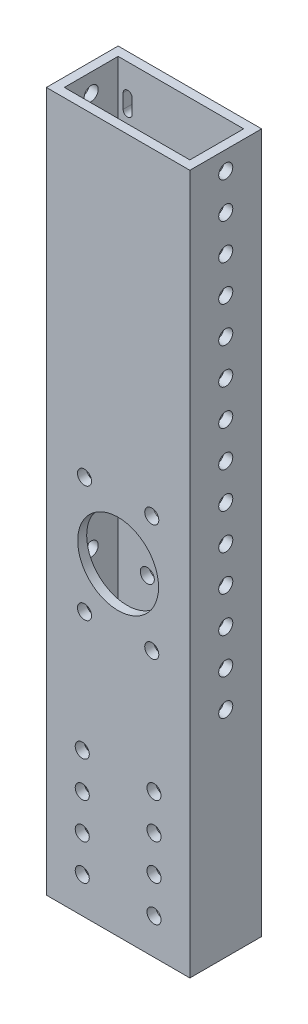
SolidWorks part; units mm, degrees
material "6061-T6 (SS)"
ref_plane "Alzado" through (0, 0, 0) normal (0, 0, 1) x (1, 0, 0)
ref_plane "Planta" through (0, 0, 0) normal (0, 1, 0) x (1, 0, 0)
ref_plane "Vista lateral" through (0, 0, 0) normal (1, 0, 0) x (0, 0, -1)
sketch "Croquis1" plane through (0, 0, 0) normal (0, 1, 0) x (1, 0, 0)
  line L1 (-101.6, -12.7) -> (101.6, -12.7)
  line L2 (-101.6, -12.7) -> (-101.6, 12.7)
  line L3 (-101.6, 12.7) -> (101.6, 12.7)
  line L4 (101.6, -12.7) -> (101.6, 12.7)
  line L5 (-101.6, -12.7) -> (101.6, 12.7) construction
  line L6 (-101.6, 12.7) -> (101.6, -12.7) construction
  point P0 (0, 0)
  dimension "D1" = 25.4
  dimension "D2" = 203.2
extrude "Saliente-Extruir1" add sketch "Croquis1" along normal blind 25.4
shell "Vaciado1" thickness 3.175 removed face at (-101.6, 12.7, 0) removed face at (101.6, 12.7, 0)
sketch "Croquis2" plane through (0, 25.4, 0) normal (0, 1, 0) x (1, 0, 0)
  line L0 (101.6, 12.7) -> (-101.6, 12.7) construction
  line L1 (-25.4, -12.7) -> (25.4, -12.7)
  line L2 (-25.4, -12.7) -> (-25.4, 12.7)
  line L3 (-25.4, 12.7) -> (25.4, 12.7)
  line L4 (25.4, -12.7) -> (25.4, 12.7)
  line L5 (-25.4, -12.7) -> (25.4, 12.7) construction
  line L6 (-25.4, 12.7) -> (25.4, -12.7) construction
  line L8 (-22.225, -9.525) -> (22.225, -9.525)
  line L9 (-22.225, -9.525) -> (-22.225, 9.525)
  line L10 (-22.225, 9.525) -> (22.225, 9.525)
  line L11 (22.225, -9.525) -> (22.225, 9.525)
  line L12 (-22.225, -9.525) -> (22.225, 9.525) construction
  line L13 (-22.225, 9.525) -> (22.225, -9.525) construction
  point P0 (0, 0)
  point P8 (0, 0)
  dimension "D1" = 50.8
  dimension "D2" = 3.175
  dimension "D3" = 3.175
extrude "Saliente-Extruir2" add sketch "Croquis2" along normal blind 247.65 separate body
sketch "Croquis3" plane through (0, 25.4, 0) normal (0, 1, 0) x (1, 0, 0)
  line L0 (0, 0) -> (0, 12.7) construction
  line L1 (25.4, 12.7) -> (-25.4, 12.7) construction
  circle A0 centre (-47.625, 0) radius 3.2639
  circle A1 centre (-79.375, 0) radius 3.2639
  circle A2 centre (79.375, 0) radius 3.2639
  circle A3 centre (47.625, 0) radius 3.2639
  dimension "D1" = 47.625
  dimension "D2" = 6.5278
  dimension "D3" = 31.75
extrude "Cortar-Extruir1" cut sketch "Croquis3" against normal through all
sketch "Croquis4" plane through (0, 0, 12.7) normal (0, 0, 1) x (1, 0, 0)
  line L0 (0, 25.4) -> (0, 139.6619) construction
  line L1 (-101.6, 25.4) -> (101.6, 25.4) construction
  line L2 (0, 139.6619) -> (-23.8125, 139.6619) construction
  circle A0 centre (0, 139.6619) radius 14.3129
  circle A1 centre (0, 139.6619) radius 23.8125 construction
  circle A2 centre (-23.8125, 139.6619) radius 2.4892 construction
  circle A3 centre (-11.9062, 160.2841) radius 2.4892
  circle A4 centre (11.9063, 160.2841) radius 2.4892
  circle A5 centre (23.8125, 139.6619) radius 2.4892 construction
  circle A6 centre (11.9062, 119.0397) radius 2.4892
  circle A7 centre (-11.9063, 119.0397) radius 2.4892
  dimension "D1" = 28.6258
  dimension "D3" = 47.625
  dimension "D4" = 4.9784
  dimension "D2" = 114.2619
  dimension "D6" = 23.8125
  dimension "D5" = 6
extrude "Cortar-Extruir2" cut sketch "Croquis4" against normal through all
sketch "Croquis8" plane through (0, 0, 12.7) normal (0, 0, 1) x (1, 0, 0)
  line L0 (0, 0) -> (0, 273.05) construction
  line L1 (-101.6, 12.7) -> (0, 12.7) construction
  line L2 (-101.6, 25.4) -> (-101.6, 0) construction
  line L3 (0, 12.7) -> (-12.7, 12.7) construction
  line L4 (0, 12.7) -> (12.7, 12.7) construction
  line L5 (-25.4, 273.05) -> (25.4, 273.05) construction
  line L6 (-12.7, 12.7) -> (-12.7, 25.4) construction
  circle A0 centre (0, 12.7) radius 2.4892
  circle A1 centre (-12.7, 12.7) radius 2.4892
  circle A2 centre (-25.4, 12.7) radius 2.4892
  circle A3 centre (-38.1, 12.7) radius 2.4892
  circle A4 centre (-50.8, 12.7) radius 2.4892
  circle A5 centre (0, 12.7) radius 2.4892
  circle A6 centre (-12.7, 12.7) radius 2.4892
  circle A7 centre (-25.4, 12.7) radius 2.4892
  circle A8 centre (-38.1, 12.7) radius 2.4892
  circle A9 centre (12.7, 12.7) radius 2.4892
  circle A10 centre (0, 12.7) radius 2.4892
  circle A11 centre (-12.7, 12.7) radius 2.4892
  circle A12 centre (-25.4, 12.7) radius 2.4892
  circle A13 centre (25.4, 12.7) radius 2.4892
  circle A14 centre (12.7, 12.7) radius 2.4892
  circle A15 centre (0, 12.7) radius 2.4892
  circle A16 centre (-12.7, 12.7) radius 2.4892
  circle A17 centre (38.1, 12.7) radius 2.4892
  circle A18 centre (25.4, 12.7) radius 2.4892
  circle A19 centre (12.7, 12.7) radius 2.4892
  circle A20 centre (0, 12.7) radius 2.4892
  circle A21 centre (12.7, 12.7) radius 2.4892
  circle A22 centre (25.4, 12.7) radius 2.4892
  circle A23 centre (38.1, 12.7) radius 2.4892
  circle A24 centre (50.8, 12.7) radius 2.4892
  circle A25 centre (-12.7, 25.4) radius 2.4892 [skipped]
  circle A26 centre (12.7, 25.4) radius 2.4892 [skipped]
  circle A27 centre (-12.7, 38.1) radius 2.4892
  circle A28 centre (12.7, 38.1) radius 2.4892
  circle A29 centre (-12.7, 50.8) radius 2.4892
  circle A30 centre (12.7, 50.8) radius 2.4892
  circle A31 centre (-12.7, 63.5) radius 2.4892
  circle A32 centre (12.7, 63.5) radius 2.4892
  circle A33 centre (-12.7, 76.2) radius 2.4892
  circle A34 centre (12.7, 76.2) radius 2.4892
  dimension "D1" = 4.9784
  dimension "D4" = 12.7
  dimension "D5" = 12.7
  dimension "D7" = 12.7
  dimension "D2" = 5
  dimension "D3" = 5
  dimension "D6" = 6
extrude "Cortar-Extruir4" cut sketch "Croquis8" against normal through all contours A4 | A3 | A2 | A1 | A0 | A9 | A13 | A17 | A24 | A28 | A29 | A30 | A31 | A32 | A34 | A33 | A27 region at (0, 12.7, 12.7) region at (-12.7, 12.7, 12.7) region at (-25.4, 12.7, 12.7) region at (-38.1, 12.7, 12.7) region at (-50.8, 12.7, 12.7) region at (12.7, 12.7, 12.7) region at (25.4, 12.7, 12.7) region at (38.1, 12.7, 12.7) region at (50.8, 12.7, 12.7) region at (12.7, 38.1, 12.7) region at (-12.7, 50.8, 12.7) region at (12.7, 50.8, 12.7) region at (-12.7, 63.5, 12.7) region at (12.7, 63.5, 12.7) region at (-12.7, 76.2, 12.7) region at (12.7, 76.2, 12.7)
sketch "Croquis6" plane through (0, 0, 12.7) normal (0, 0, 1) x (1, 0, 0)
  line L0 (25.4, 273.05) -> (25.4, 25.4) construction
  line L1 (-25.4, 88.646) -> (25.4, 88.646)
  line L2 (-25.4, 88.646) -> (-25.4, 114.046)
  line L3 (-25.4, 114.046) -> (25.4, 114.046)
  line L4 (25.4, 88.646) -> (25.4, 114.046)
  line L5 (-25.4, 88.646) -> (25.4, 114.046) construction
  line L6 (-25.4, 114.046) -> (25.4, 88.646) construction
  line L7 (-101.6, 25.4) -> (101.6, 25.4) construction
  line L9 (-22.225, 91.821) -> (22.225, 91.821)
  line L10 (-22.225, 91.821) -> (-22.225, 110.871)
  line L11 (-22.225, 110.871) -> (22.225, 110.871)
  line L12 (22.225, 91.821) -> (22.225, 110.871)
  line L13 (-22.225, 91.821) -> (22.225, 110.871) construction
  line L14 (-22.225, 110.871) -> (22.225, 91.821) construction
  point P0 (0, 101.346)
  point P11 (0, 101.346)
  dimension "D1" = 25.4
  dimension "D2" = 63.246
  dimension "D3" = 3.175
  dimension "D4" = 3.175
extrude "Saliente-Extruir3" add sketch "Croquis6" along normal blind 69.85 separate body
sketch "Croquis7" plane through (0, 114.046, 0) normal (0, 1, 0) x (1, 0, 0)
  line L0 (0, -12.7) -> (0, -82.55) construction
  line L1 (-25.4, -12.7) -> (25.4, -12.7) construction
  line L2 (25.4, -82.55) -> (-25.4, -82.55) construction
  line L3 (16.51, -12.7) -> (-16.51, -12.7)
  line L4 (25.4, -12.7) -> (-25.4, -12.7) construction
  line L5 (-16.51, -12.7) -> (-16.51, -34.798)
  line L6 (-13.208, -38.1) -> (13.208, -38.1)
  line L7 (16.51, -12.7) -> (16.51, -34.798)
  arc A0 (16.51, -34.798) -> (13.208, -38.1) centre (13.208, -34.798) cw
  arc A1 (-16.51, -34.798) -> (-13.208, -38.1) centre (-13.208, -34.798) ccw
  point P12 (0, -38.1)
  point P16 (16.51, -38.1)
  point P19 (-16.51, -38.1)
  dimension "D3" = 3.302
  dimension "D1" = 25.4
  dimension "D2" = 33.02
extrude "Cortar-Extruir3" cut sketch "Croquis7" against normal up to next (3.175 mm away)
sketch "Croquis11" plane through (25.4, 0, 0) normal (1, 0, 0) x (0, 0, -1)
  line L0 (0, -101.854) -> (-381, -101.854) construction
  line L1 (-82.55, 88.646) -> (-82.55, 114.046) construction
  line L2 (-82.55, 88.646) -> (-12.7, 88.646) construction
  line L6 (-517.96, -101.854) -> (-276.66, -101.854) construction
  line L7 (-517.96, -101.854) -> (-517.96, 139.446) construction
  line L8 (-517.96, 139.446) -> (-276.66, 139.446) construction
  line L9 (-276.66, -101.854) -> (-276.66, 139.446) construction
  circle A0 centre (-396.875, 145.796) radius 38.1
  dimension "D3" = 76.2
  dimension "D4" = 209.55
  dimension "D5" = 276.225
  dimension "D1" = 190.5
  dimension "D2" = 381
  dimension "D6" = 241.3
sketch "Croquis9" plane through (0, 0, 12.7) normal (0, 0, 1) x (1, 0, 0)
  line L0 (0, 0) -> (0, 273.05) construction
  line L1 (-25.4, 273.05) -> (25.4, 273.05) construction
  line L2 (50.8, 0) -> (-50.8, 0)
  line L3 (-101.6, 0) -> (101.6, 0) construction
  line L4 (-57.15, 6.35) -> (-57.15, 23.7481)
  line L5 (-101.6, 25.4) -> (101.6, 25.4) construction
  line L6 (-56.3451, 26.8425) -> (-27.2168, 79.0403)
  line L7 (-25.4, 273.05) -> (-25.4, 25.4) construction
  line L8 (-21.6717, 82.296) -> (21.6717, 82.296)
  line L9 (56.3451, 26.8425) -> (27.2168, 79.0403)
  line L10 (57.15, 6.35) -> (57.15, 23.7481)
  line L11 (-25.4, 88.646) -> (25.4, 88.646) construction
  circle A0 centre (-50.8, 12.7) radius 2.4892 construction
  arc A2 (-50.8, 0) -> (-57.15, 6.35) centre (-50.8, 6.35) cw
  arc A3 (-57.15, 23.7481) -> (-56.3451, 26.8425) centre (-50.8, 23.7481) cw
  arc A4 (-27.2168, 79.0403) -> (-21.6717, 82.296) centre (-21.6717, 75.946) cw
  arc A5 (27.2168, 79.0403) -> (21.6717, 82.296) centre (21.6717, 75.946) ccw
  arc A6 (57.15, 23.7481) -> (56.3451, 26.8425) centre (50.8, 23.7481) ccw
  arc A7 (50.8, 0) -> (57.15, 6.35) centre (50.8, 6.35) ccw
  circle A9 centre (-25.4, 12.7) radius 2.4892
  circle A10 centre (-25.4, 12.7) radius 2.4892
  circle A11 centre (-12.7, 12.7) radius 2.4892
  circle A12 centre (-12.7, 12.7) radius 2.4892
  circle A13 centre (0, 12.7) radius 2.4892
  circle A14 centre (0, 12.7) radius 2.4892
  circle A15 centre (0, 12.7) radius 2.4892
  circle A16 centre (0, 12.7) radius 2.4892
  circle A17 centre (12.7, 12.7) radius 2.4892
  circle A18 centre (12.7, 12.7) radius 2.4892
  circle A19 centre (-38.1, 12.7) radius 2.4892
  circle A20 centre (-38.1, 12.7) radius 2.4892
  circle A21 centre (-25.4, 12.7) radius 2.4892
  circle A22 centre (-25.4, 12.7) radius 2.4892
  circle A23 centre (-12.7, 12.7) radius 2.4892
  circle A24 centre (-12.7, 12.7) radius 2.4892
  circle A25 centre (0, 12.7) radius 2.4892
  circle A26 centre (0, 12.7) radius 2.4892
  circle A27 centre (-50.8, 12.7) radius 2.4892
  circle A28 centre (-50.8, 12.7) radius 2.4892
  circle A29 centre (-38.1, 12.7) radius 2.4892
  circle A30 centre (-38.1, 12.7) radius 2.4892
  circle A31 centre (25.4, 12.7) radius 2.4892
  circle A32 centre (25.4, 12.7) radius 2.4892
  circle A33 centre (38.1, 12.7) radius 2.4892
  circle A34 centre (38.1, 12.7) radius 2.4892
  circle A35 centre (-12.7, 12.7) radius 2.4892
  circle A36 centre (-12.7, 12.7) radius 2.4892
  circle A37 centre (0, 12.7) radius 2.4892
  circle A38 centre (0, 12.7) radius 2.4892
  circle A39 centre (12.7, 12.7) radius 2.4892
  circle A40 centre (12.7, 12.7) radius 2.4892
  circle A41 centre (25.4, 12.7) radius 2.4892
  circle A42 centre (25.4, 12.7) radius 2.4892
  circle A43 centre (-25.4, 12.7) radius 2.4892
  circle A44 centre (-25.4, 12.7) radius 2.4892
  circle A45 centre (-12.7, 12.7) radius 2.4892
  circle A46 centre (-12.7, 12.7) radius 2.4892
  circle A47 centre (50.8, 12.7) radius 2.4892
  circle A48 centre (50.8, 12.7) radius 2.4892
  circle A49 centre (38.1, 12.7) radius 2.4892
  circle A50 centre (38.1, 12.7) radius 2.4892
  circle A51 centre (25.4, 12.7) radius 2.4892
  circle A52 centre (25.4, 12.7) radius 2.4892
  circle A53 centre (12.7, 12.7) radius 2.4892
  circle A54 centre (12.7, 12.7) radius 2.4892
  circle A55 centre (0, 12.7) radius 2.4892
  circle A56 centre (0, 12.7) radius 2.4892
  circle A57 centre (12.7, 12.7) radius 2.4892
  circle A58 centre (12.7, 12.7) radius 2.4892
  circle A59 centre (-12.7, 76.2) radius 2.4892
  circle A60 centre (-12.7, 76.2) radius 2.4892
  circle A61 centre (12.7, 63.5) radius 2.4892
  circle A62 centre (12.7, 63.5) radius 2.4892
  circle A63 centre (-12.7, 63.5) radius 2.4892
  circle A64 centre (-12.7, 63.5) radius 2.4892
  circle A65 centre (12.7, 50.8) radius 2.4892
  circle A66 centre (12.7, 50.8) radius 2.4892
  circle A67 centre (-12.7, 50.8) radius 2.4892
  circle A68 centre (-12.7, 50.8) radius 2.4892
  circle A69 centre (12.7, 38.1) radius 2.4892
  circle A70 centre (12.7, 38.1) radius 2.4892
  circle A71 centre (-12.7, 38.1) radius 2.4892
  circle A72 centre (-12.7, 38.1) radius 2.4892
  circle A73 centre (12.7, 76.2) radius 2.4892
  circle A74 centre (12.7, 76.2) radius 2.4892
  point P22 (-57.15, 0)
  point P25 (-57.15, 25.4)
  point P28 (-25.4, 82.296)
  point P38 (0, 82.296)
  dimension "D1" = 6.35
  dimension "D3" = 6.35
  dimension "D37" = 6.35
  dimension "D4" = 0
  dimension "D5" = 0
  dimension "D6" = 0
  dimension "D7" = 0
  dimension "D8" = 0
  dimension "D9" = 0
  dimension "D10" = 0
  dimension "D11" = 0
  dimension "D12" = 0
  dimension "D13" = 0
  dimension "D14" = 0
  dimension "D15" = 0
  dimension "D16" = 0
  dimension "D17" = 0
  dimension "D18" = 0
  dimension "D19" = 0
  dimension "D20" = 0
  dimension "D21" = 0
  dimension "D22" = 0
  dimension "D23" = 0
  dimension "D24" = 0
  dimension "D25" = 0
  dimension "D26" = 0
  dimension "D27" = 0
  dimension "D28" = 0
  dimension "D29" = 0
  dimension "D30" = 0
  dimension "D31" = 0
  dimension "D32" = 0
  dimension "D33" = 0
  dimension "D34" = 0
  dimension "D35" = 0
  dimension "D36" = 0
extrude "Saliente-Extruir4" add sketch "Croquis9" along normal blind 6.35 separate body contours L0 L8 A4 L6 A3 A60 A64 A68 A72 | L0 A6 L9 A5 L8 A74 A70 A66 A62 | L0 A3 L4 A2 | L0 L2 A7 L10 A6 A56 region at (-24.3725, 36.0328, 12.7) region at (24.3725, 36.0328, 12.7)
sketch "Croquis15" plane through (25.4, 0, 0) normal (1, 0, 0) x (0, 0, -1)
  line L0 (-12.7, 0) -> (-12.7, 171.1325) construction
  line L1 (-12.7, 273.05) -> (-12.7, 25.4) construction
  line L2 (-72.5746, 227.1642) -> (-41.5317, 154.1315) construction
  line L3 (-105.4538, 208.2656) -> (-57.9713, 144.6822) construction
  line L4 (-94.6246, 238.2605) -> (-401.3483, 164.3633) construction
  line L5 (-392.4017, 127.2287) -> (-85.6779, 201.1258) construction
  line L8 (-82.55, 114.046) -> (-12.7, 114.046) construction
  circle A0 centre (-50.32, 150.396) radius 30
  arc A1 (-57.9713, 144.6822) -> (-41.5317, 154.1315) centre (-50.32, 150.396) ccw construction
  arc A2 (-401.3483, 164.3633) -> (-392.4017, 127.2287) centre (-396.875, 145.796) ccw construction
  arc A3 (-72.5746, 227.1642) -> (-105.4538, 208.2656) centre (-90.1513, 219.6932) ccw construction
  arc A4 (-85.6779, 201.1258) -> (-94.6246, 238.2605) centre (-90.1513, 219.6932) ccw construction
  dimension "D2" = 60
  dimension "D3" = 19.0986
  dimension "D4" = 38.1972
  dimension "D1" = 171.1325
  dimension "D7" = 6.35
  dimension "D8" = 7.62
sketch "Croquis16" plane through (25.4, 0, 0) normal (1, 0, 0) x (0, 0, -1)
  line L0 (-50.32, 150.396) -> (-50.32, 175.796) construction
  line L1 (-13.329, 272.9215) -> (-117.7691, 251.586)
  line L2 (-82.55, 94.996) -> (-82.55, 113.9625)
  line L3 (-82.5522, 114.1295) -> (-83.4835, 149.5234)
  line L4 (-76.2, 88.646) -> (6.35, 88.646)
  line L5 (12.7, 273.05) -> (12.7, 25.4) construction
  line L6 (12.7, 94.996) -> (12.7, 266.7)
  line L7 (6.35, 273.05) -> (-12.058, 273.05)
  line L9 (-122.7196, 244.0935) -> (-110.5184, 184.367)
  line L10 (-94.6246, 238.2605) -> (-401.3483, 164.3633) construction
  circle A0 centre (-90.1513, 219.6932) radius 14.3256
  circle A1 centre (-50.32, 150.396) radius 33.175
  circle A4 centre (-50.32, 150.396) radius 9.5631
  circle A5 centre (-50.32, 150.396) radius 25.4 construction
  circle A6 centre (-50.32, 175.796) radius 2.4892
  circle A7 centre (-32.3595, 168.3565) radius 2.4892 construction
  circle A8 centre (-24.92, 150.396) radius 2.4892
  circle A9 centre (-32.3595, 132.4355) radius 2.4892
  circle A10 centre (-50.32, 124.996) radius 2.4892
  circle A11 centre (-68.2805, 132.4355) radius 2.4892
  circle A12 centre (-75.72, 150.396) radius 2.4892
  circle A13 centre (-68.2805, 168.3565) radius 2.4892
  arc A18 (-105.4068, 178.645) -> (-83.4801, 149.4007) centre (-115.2158, 148.4482) cw
  arc A19 (-110.5184, 184.367) -> (-105.4068, 178.645) centre (-103.0526, 185.8922) ccw
  arc A21 (-117.7691, 251.586) -> (-122.7196, 244.0935) centre (-116.4981, 245.3645) ccw
  arc A23 (-12.058, 273.05) -> (-13.329, 272.9215) centre (-12.058, 266.7) ccw
  circle A26 centre (-50.32, 150.396) radius 30 construction
  arc A29 (-82.55, 113.9625) -> (-82.5522, 114.1295) centre (-88.9, 113.9625) ccw
  arc A31 (12.7, 266.7) -> (6.35, 273.05) centre (6.35, 266.7) ccw
  arc A32 (6.35, 88.646) -> (12.7, 94.996) centre (6.35, 94.996) ccw
  arc A33 (-82.55, 94.996) -> (-76.2, 88.646) centre (-76.2, 94.996) ccw
  point P45 (-12.7, 273.05)
  point P72 (-82.55, 114.046)
  point P74 (12.7, 273.05)
  point P77 (12.7, 88.646)
  point P80 (-82.55, 88.646)
  dimension "D1" = 28.6512
  dimension "D2" = 3.175
  dimension "D3" = 31.75
  dimension "D4" = 19.1262
  dimension "D5" = 50.8
  dimension "D6" = 4.9784
  dimension "D9" = 7.62
  dimension "D10" = 6.35
  dimension "D13" = 60.96
  dimension "D14" = 6.35
  dimension "D15" = 6.35
  dimension "D12" = 6.35
  dimension "D8" = 25.4
  dimension "D11" = 12.7
  dimension "D16" = 2
  dimension "D7" = 8
extrude "Saliente-Extruir5" add sketch "Croquis16" along normal blind 6.35 separate body contours L4 A32 A31 A23 | L2 A33 L4 A23 L1 A21 L9 A19 A18 A1 L3 A29 A0 | A1 A13 A12 A11 A10 A9 A8 A6 A4 region at (25.4, 189.4289, 39.9715) region at (25.4, 182.6299, 50.744)
sketch "Croquis12" plane through (25.4, 0, 0) normal (1, 0, 0) x (0, 0, -1)
  line L0 (-82.55, 101.346) -> (-12.7, 101.346) construction
  line L1 (-82.55, 88.646) -> (-82.55, 114.046) construction
  line L2 (-12.7, 88.646) -> (-12.7, 114.046) construction
  line L3 (0, 273.05) -> (0, 0) construction
  line L4 (-12.7, 273.05) -> (12.7, 273.05) construction
  line L5 (0, 101.346) -> (-12.7, 101.346) construction
  line L6 (0, 101.346) -> (0, 114.046) construction
  circle A1 centre (0, 101.346) radius 2.4892
  circle A2 centre (-12.7, 101.346) radius 2.4892 [skipped]
  circle A3 centre (-25.4, 101.346) radius 2.4892
  circle A4 centre (-38.1, 101.346) radius 2.4892
  circle A5 centre (-50.8, 101.346) radius 2.4892
  circle A6 centre (0, 114.046) radius 2.4892
  circle A7 centre (0, 126.746) radius 2.4892
  circle A8 centre (0, 139.446) radius 2.4892
  circle A9 centre (0, 152.146) radius 2.4892
  circle A10 centre (0, 164.846) radius 2.4892
  circle A11 centre (0, 177.546) radius 2.4892
  circle A12 centre (0, 190.246) radius 2.4892
  circle A13 centre (0, 202.946) radius 2.4892
  circle A14 centre (0, 215.646) radius 2.4892
  circle A15 centre (0, 228.346) radius 2.4892
  circle A16 centre (0, 241.046) radius 2.4892
  circle A17 centre (0, 253.746) radius 2.4892
  circle A18 centre (0, 266.446) radius 2.4892
  circle A19 centre (-63.5, 101.346) radius 2.4892
  circle A20 centre (-76.2, 101.346) radius 2.4892
  dimension "D1" = 4.9784
  dimension "D3" = 12.7
  dimension "D5" = 12.7
  dimension "D2" = 7
  dimension "D4" = 14
extrude "Cortar-Extruir5" cut sketch "Croquis12" against normal through all and the other way through all
sketch "Croquis17" plane through (31.75, 0, 0) normal (1, 0, 0) x (0, 0, -1)
  line L0 (-403.8236, 170.2271) -> (-118.0462, 251.5072)
  line L1 (-117.4868, 251.6437) -> (-21.8452, 271.1818)
  line L3 (-122.7196, 244.0935) -> (-110.5184, 184.367) construction
  line L4 (-12.7, 273.05) -> (-12.7, 25.4) construction
  line L5 (-12.7, 206.2243) -> (-12.7, 263.716)
  line L6 (-411.78, 166.363) -> (-373.2477, 194.2875)
  line L8 (-136.7418, 185.5575) -> (-321.1054, 141.1398)
  line L9 (-13.329, 272.9215) -> (-117.7691, 251.586) construction
  line L10 (-392.4017, 127.2287) -> (-85.6779, 201.1258) construction
  line L11 (-321.1054, 141.1398) -> (-371.9054, 141.1398)
  circle A0 centre (-396.875, 145.796) radius 14.3256
  circle A1 centre (-90.1513, 219.6932) radius 14.3256
  circle A2 centre (-396.875, 145.796) radius 25.4
  arc A3 (-118.0462, 251.5072) -> (-117.4868, 251.6437) centre (-115.9616, 244.1779) cw
  arc A4 (-21.8452, 271.1818) -> (-12.7, 263.716) centre (-20.32, 263.716) cw
  arc A5 (-12.7, 206.2243) -> (-43.5311, 181.4117) centre (-38.1, 206.2243) cw
  circle A6 centre (-50.32, 150.396) radius 31.75
  arc A10 (-368.4979, 195.7323) -> (-273.9823, 207.1562) centre (-357.3657, 500.3289) ccw
  arc A13 (-90.6096, 168.5131) -> (-75.8725, 169.2409) centre (-83.5383, 174.8944) ccw
  circle A15 centre (-368.7762, 188.1174) radius 7.62
  circle A17 centre (-116.2498, 180.6969) radius 6.35
  circle A18 centre (-396.875, 145.796) radius 38.1 construction
  circle A19 centre (-368.7762, 188.1174) radius 6.35 construction
  arc A20 (-83.4801, 149.4007) -> (-105.4068, 178.645) centre (-115.2158, 148.4482) ccw construction
  arc A24 (-90.6096, 168.5131) -> (-114.2186, 174.6806) centre (-107.1094, 153.6233) ccw
  arc A25 (-136.7418, 185.5575) -> (-122.089, 178.2015) centre (-133.7672, 173.2107) cw
  circle A26 centre (-103.445, 184.6843) radius 6.35
  arc A28 (-110.5184, 184.367) -> (-105.4068, 178.645) centre (-103.0526, 185.8922) ccw construction
  arc A30 (-83.484, 149.5233) -> (-105.4068, 178.645) centre (-115.2158, 148.4482) ccw construction
  point P19 (-117.7691, 251.586)
  dimension "D1" = 28.6512
  dimension "D2" = 50.8
  dimension "D3" = 7.62
  dimension "D4" = 63.5
  dimension "D5" = 9.525
  dimension "D6" = 25.4
  dimension "D7" = 50.8
  dimension "D8" = 12.7
  dimension "D9" = 15.24
  dimension "D10" = 12.7
  dimension "D11" = 304.8
  dimension "D12" = 76.2
  dimension "D13" = 12.7
  dimension "D16" = 12.7
  dimension "D17" = 12.7
  dimension "D18" = 22.225
  dimension "D14" = 3.175
  dimension "D15" = 50.8
extrude "Saliente-Extruir6" add sketch "Croquis17" along normal blind 6.35 separate body contours A2 L0 | L5 A4 A3 L0 | A2 A0 | A2 L0 | A15 | A15 L0 | A17 | A26 region at (31.75, 200.7242, 175.8834) region at (31.75, 192.4732, 340.2276) region at (31.75, 179.8601, 385.7751) region at (31.75, 188.1174, 368.7762) region at (31.75, 165.4916, 382.0001) region at (31.75, 180.6969, 116.2498) region at (31.75, 184.6843, 103.445)
sketch "Croquis18" plane through (38.1, 0, 0) normal (1, 0, 0) x (0, 0, -1)
  line L0 (-122.7196, 244.0935) -> (-110.5184, 184.367) construction
  line L1 (-122.5235, 243.1334) -> (-110.0283, 181.9679)
  line L2 (-403.8236, 170.2271) -> (-118.0462, 251.5072) construction
  line L5 (-411.78, 166.363) -> (-373.2477, 194.2875) construction
  line L7 (-403.8236, 170.2271) -> (-130.4821, 247.9702)
  line L8 (-411.78, 166.363) -> (-373.2477, 194.2875)
  line L9 (-136.7418, 185.5575) -> (-321.1054, 141.1398) construction
  line L12 (-321.1054, 141.1398) -> (-371.9054, 141.1398) construction
  line L13 (-321.1054, 141.1398) -> (-371.9054, 141.1398)
  line L14 (-136.7418, 185.5575) -> (-321.1054, 141.1398)
  circle A1 centre (-396.875, 145.796) radius 25.4
  circle A2 centre (-396.875, 145.796) radius 25.4
  circle A5 centre (-396.875, 145.796) radius 14.3256
  circle A6 centre (-396.875, 145.796) radius 14.3256
  arc A12 (-122.5235, 243.1334) -> (-130.4821, 247.9702) centre (-128.745, 241.8624) ccw
  arc A13 (-368.4979, 195.7323) -> (-273.9823, 207.1562) centre (-357.3657, 500.3289) ccw construction
  arc A14 (-122.089, 178.2015) -> (-114.2186, 174.6806) centre (-116.2498, 180.6969) ccw construction
  arc A15 (-122.089, 178.2015) -> (-136.7418, 185.5575) centre (-133.7672, 173.2107) ccw construction
  arc A17 (-368.4979, 195.7323) -> (-373.2477, 194.2875) centre (-368.7762, 188.1174) ccw construction
  arc A18 (-368.4979, 195.7323) -> (-273.9823, 207.1562) centre (-357.3657, 500.3289) ccw
  arc A19 (-368.4979, 195.7323) -> (-373.2477, 194.2875) centre (-368.7762, 188.1174) ccw
  arc A20 (-122.089, 178.2015) -> (-114.2186, 174.6806) centre (-116.2498, 180.6969) ccw
  arc A21 (-122.089, 178.2015) -> (-136.7418, 185.5575) centre (-133.7672, 173.2107) ccw
  circle A22 centre (-116.2498, 180.6969) radius 6.35
  dimension "D2" = 6.35
  dimension "D1" = 0
  dimension "D3" = 0
extrude "Saliente-Extruir7" add sketch "Croquis18" along normal blind 6.35 from surface separate body contours L1 A12 A2 | A2 | A2 L7 | A22 region at (38.1, 189.052, 239.9072) region at (38.1, 180.6969, 116.2498) region at (38.1, 187.7771, 359.9808) region at (38.1, 165.4916, 382.0001) starting at face at (25.4, 101.346, -2.4892)
sketch "Croquis22" plane through (38.1, 0, 0) normal (1, 0, 0) x (0, 0, -1)
  line L0 (-396.875, 145.796) -> (-90.1513, 219.6932) construction
  line L1 (-90.1513, 219.6932) -> (-50.32, 150.396) construction
  line L4 (-273.9823, 207.1562) -> (-118.0462, 251.5072) construction
  line L5 (-21.8452, 271.1818) -> (-117.4868, 251.6437) construction
  line L6 (-122.7196, 244.0935) -> (-110.5184, 184.367) construction
  circle A1 centre (-347.4881, 157.6945) radius 3.2639
  circle A2 centre (-396.875, 145.796) radius 19.0986 construction
  arc A3 (-401.3483, 164.3633) -> (-392.4017, 127.2287) centre (-396.875, 145.796) ccw construction
  circle A4 centre (-347.4881, 157.6945) radius 6.35 construction
  circle A7 centre (-72.747, 189.4137) radius 3.2639
  circle A8 centre (-72.747, 189.4137) radius 6.35 construction
  circle A9 centre (-50.32, 213.896) radius 6.35 construction
  circle A10 centre (-50.32, 213.896) radius 3.2639
  circle A15 centre (-72.747, 254.3022) radius 3.2639
  circle A16 centre (-72.747, 254.3022) radius 6.35 construction
  circle A17 centre (-20.32, 263.716) radius 6.35 construction
  circle A18 centre (-20.32, 263.716) radius 3.2639
  circle A19 centre (-368.7762, 188.1174) radius 3.2639
  circle A22 centre (-116.2498, 180.6969) radius 6.35 construction
  circle A23 centre (-116.2498, 180.6969) radius 3.2639
  circle A24 centre (-116.4981, 245.3645) radius 6.35 construction
  circle A25 centre (-116.4981, 245.3645) radius 3.2639
  arc A26 (-122.089, 178.2015) -> (-114.2186, 174.6806) centre (-116.2498, 180.6969) ccw construction
  circle A27 centre (-129.97, 241.514) radius 3.2639
  circle A28 centre (-129.97, 241.514) radius 6.35 construction
  circle A30 centre (-103.445, 184.6843) radius 6.35 construction
  circle A31 centre (-103.445, 184.6843) radius 3.2639
  arc A32 (-110.5184, 184.367) -> (-105.4068, 178.645) centre (-103.0526, 185.8922) ccw construction
  arc A33 (-83.4801, 149.4007) -> (-105.4068, 178.645) centre (-115.2158, 148.4482) ccw construction
  dimension "D1" = 6.5278
  dimension "D2" = 50.8
  dimension "D3" = 12.7
  dimension "D4" = 34.925
  dimension "D5" = 63.5
  dimension "D6" = 7.62
  dimension "D9" = 6.5278
extrude "Cortar-Extruir6" cut sketch "Croquis22" against normal through all
sketch "Croquis24" plane through (38.1, 0, 0) normal (1, 0, 0) x (0, 0, -1)
  line L0 (-396.875, 145.796) -> (-90.1513, 219.6932) construction
  line L1 (-243.5131, 182.7446) -> (-247.9864, 201.3119) construction
  line L2 (-94.6246, 238.2605) -> (-401.3483, 164.3633) construction
  circle A0 centre (-295.9867, 170.1024) radius 2.4892
  circle A1 centre (-191.0395, 195.3867) radius 2.4892
  circle A2 centre (-243.5131, 182.7446) radius 2.4892
  circle A3 centre (-147.826, 205.7979) radius 2.4892
  dimension "D1" = 4.9784
  dimension "D2" = 53.975
  dimension "D3" = 44.45
sketch "Croquis25" plane through (31.75, 0, 0) normal (1, 0, 0) x (0, 0, -1)
  line L0 (-12.7, 0) -> (-12.7, 139.7) construction
  line L1 (-12.7, 123.825) -> (-12.7, 155.575)
  line L2 (-12.7, 0) -> (-12.7, 171.1325) construction
  line L3 (-15.875, 158.75) -> (-17.145, 158.75)
  line L4 (-20.32, 155.575) -> (-20.32, 123.825)
  line L5 (-12.7, 139.7) -> (-20.32, 139.7) construction
  line L6 (-15.875, 120.65) -> (-17.145, 120.65)
  arc A0 (-12.7, 155.575) -> (-15.875, 158.75) centre (-15.875, 155.575) ccw
  arc A1 (-15.875, 120.65) -> (-12.7, 123.825) centre (-15.875, 123.825) ccw
  arc A2 (-17.145, 120.65) -> (-20.32, 123.825) centre (-17.145, 123.825) cw
  arc A3 (-17.145, 158.75) -> (-20.32, 155.575) centre (-17.145, 155.575) ccw
  point P13 (-12.7, 158.75)
  point P16 (-12.7, 120.65)
  point P19 (-20.32, 120.65)
  point P22 (-20.32, 158.75)
  dimension "D4" = 3.175
  dimension "D1" = 139.7
  dimension "D2" = 7.62
  dimension "D3" = 38.1
extrude "Cortar-Extruir8" cut sketch "Croquis25" against normal through all
extrude "Cortar-Extruir9" [suppressed] cut sketch "Croquis24" against normal through all
fillet "Redondeo1" [suppressed] radius 50.8
fillet "Redondeo2" [suppressed] radius 50.8
delete or keep bodies "Sólido-Eliminar/Conservar 1" type keep bodies bodies 112
delete or keep bodies "Sólido-Eliminar/Conservar 2" [suppressed] type keep bodies bodies 111
delete or keep bodies "Sólido-Eliminar/Conservar 3" [suppressed] type keep bodies bodies 107
delete or keep bodies "Sólido-Eliminar/Conservar 4" [suppressed] type keep bodies bodies 109
delete or keep bodies "Sólido-Eliminar/Conservar 5" [suppressed] type keep bodies bodies 121
delete or keep bodies "Sólido-Eliminar/Conservar 6" [suppressed] type keep bodies bodies 125
sketch "Croquis29" [suppressed] plane through (0, 0, 0) normal (1, 0, 0) x (0, 0, -1)
  line L0 (-392.4017, 127.2287) -> (-85.6779, 201.1258) construction
  line L1 (-94.6246, 238.2605) -> (-401.3483, 164.3633) construction
  line L2 (-392.4017, 127.2287) -> (-85.6779, 201.1258) construction
  line L3 (-94.6246, 238.2605) -> (-401.3483, 164.3633) construction
  line L4 (-392.8842, 129.2314) -> (-86.1604, 203.1285)
  line L5 (-94.1421, 236.2578) -> (-400.8658, 162.3606)
  line L6 (-391.9941, 125.5371) -> (-85.2704, 199.4342)
  line L7 (-95.0321, 239.9521) -> (-401.7559, 166.0549)
  arc A0 (-85.6779, 201.1258) -> (-94.6246, 238.2605) centre (-90.1513, 219.6932) ccw construction
  arc A1 (-401.3483, 164.3633) -> (-392.4017, 127.2287) centre (-396.875, 145.796) ccw construction
  arc A2 (-85.6779, 201.1258) -> (-94.6246, 238.2605) centre (-90.1513, 219.6932) ccw construction
  arc A3 (-401.3483, 164.3633) -> (-392.4017, 127.2287) centre (-396.875, 145.796) ccw construction
  arc A4 (-86.1604, 203.1285) -> (-94.1421, 236.2578) centre (-90.1513, 219.6932) ccw
  arc A5 (-400.8658, 162.3606) -> (-392.8842, 129.2314) centre (-396.875, 145.796) ccw
  arc A6 (-401.7559, 166.0549) -> (-391.9941, 125.5371) centre (-396.875, 145.796) ccw
  arc A7 (-85.2704, 199.4342) -> (-95.0321, 239.9521) centre (-90.1513, 219.6932) ccw
  dimension "D1" = 2.06
  dimension "D2" = 3.8
extrude "Saliente-Extruir9" [suppressed] add sketch "Croquis29" along normal mid plane 9 separate body
sketch "Croquis30" [suppressed] plane through (0, 0, 0) normal (1, 0, 0) x (0, 0, -1)
  line L0 (-72.5746, 227.1642) -> (-41.5317, 154.1315) construction
  line L1 (-105.4538, 208.2656) -> (-57.9713, 144.6822) construction
  line L2 (-72.5746, 227.1642) -> (-41.5317, 154.1315) construction
  line L3 (-105.4538, 208.2656) -> (-57.9713, 144.6822) construction
  line L4 (-74.4704, 226.3584) -> (-43.4275, 153.3257)
  line L5 (-103.8032, 209.4982) -> (-56.3207, 145.9148)
  line L6 (-106.8479, 207.2245) -> (-59.3654, 143.6411)
  line L7 (-70.9732, 227.8449) -> (-39.9303, 154.8122)
  arc A0 (-57.9713, 144.6822) -> (-41.5317, 154.1315) centre (-50.32, 150.396) ccw construction
  arc A1 (-72.5746, 227.1642) -> (-105.4538, 208.2656) centre (-90.1513, 219.6932) ccw construction
  arc A2 (-57.9713, 144.6822) -> (-41.5317, 154.1315) centre (-50.32, 150.396) ccw construction
  arc A3 (-72.5746, 227.1642) -> (-105.4538, 208.2656) centre (-90.1513, 219.6932) ccw construction
  arc A4 (-56.3207, 145.9148) -> (-43.4275, 153.3257) centre (-50.32, 150.396) ccw
  arc A5 (-74.4704, 226.3584) -> (-103.8032, 209.4982) centre (-90.1513, 219.6932) ccw
  arc A6 (-70.9732, 227.8449) -> (-106.8479, 207.2245) centre (-90.1513, 219.6932) ccw
  arc A7 (-59.3654, 143.6411) -> (-39.9303, 154.8122) centre (-50.32, 150.396) ccw
  dimension "D1" = 2.06
  dimension "D2" = 3.8
extrude "Saliente-Extruir10" [suppressed] add sketch "Croquis30" along normal mid plane 15 separate body
delete or keep bodies "Sólido-Eliminar/Conservar 7" [suppressed] type keep bodies bodies 123
delete or keep bodies "Sólido-Eliminar/Conservar 8" [suppressed] type keep bodies bodies 124
delete or keep bodies "Sólido-Eliminar/Conservar 9" [suppressed] type keep bodies bodies 126
delete or keep bodies "Sólido-Eliminar/Conservar 11" [suppressed] type keep bodies bodies 125
sketch "Croquis31" plane through (0, 0, -12.7) normal (0, 0, -1) x (-1, 0, 0)
  line L0 (0, 273.05) -> (0, 25.4) construction
  line L1 (-25.4, 273.05) -> (25.4, 273.05) construction
  line L2 (-25.4, 25.4) -> (25.4, 25.4) construction
  line L3 (-17.272, 238.125) -> (0, 238.125) construction
  line L4 (-17.272, 203.2) -> (17.272, 203.2) construction
  line L5 (-17.272, 203.2) -> (-17.272, 273.05) construction
  line L6 (-17.272, 273.05) -> (17.272, 273.05) construction
  line L7 (17.272, 203.2) -> (17.272, 273.05) construction
  line L8 (-17.272, 203.2) -> (17.272, 273.05) construction
  line L9 (-17.272, 273.05) -> (17.272, 203.2) construction
  line L10 (-18.8595, 257.683) -> (-18.8595, 262.763) construction
  line L11 (-20.447, 257.683) -> (-20.447, 262.763)
  line L12 (-17.272, 257.683) -> (-17.272, 262.763)
  line L13 (-18.8595, 218.567) -> (-18.8595, 213.487) construction
  line L14 (-20.447, 218.567) -> (-20.447, 213.487)
  line L15 (-17.272, 218.567) -> (-17.272, 213.487)
  line L16 (18.8595, 218.567) -> (18.8595, 213.487) construction
  line L17 (20.447, 218.567) -> (20.447, 213.487)
  line L18 (17.272, 218.567) -> (17.272, 213.487)
  line L19 (18.8595, 257.683) -> (18.8595, 262.763) construction
  line L20 (20.447, 257.683) -> (20.447, 262.763)
  line L21 (17.272, 257.683) -> (17.272, 262.763)
  arc A0 (-20.447, 257.683) -> (-17.272, 257.683) centre (-18.8595, 257.683) ccw
  arc A1 (-17.272, 262.763) -> (-20.447, 262.763) centre (-18.8595, 262.763) ccw
  arc A2 (-20.447, 218.567) -> (-17.272, 218.567) centre (-18.8595, 218.567) cw
  arc A3 (-17.272, 213.487) -> (-20.447, 213.487) centre (-18.8595, 213.487) cw
  arc A4 (20.447, 218.567) -> (17.272, 218.567) centre (18.8595, 218.567) ccw
  arc A5 (17.272, 213.487) -> (20.447, 213.487) centre (18.8595, 213.487) ccw
  arc A6 (20.447, 257.683) -> (17.272, 257.683) centre (18.8595, 257.683) cw
  arc A7 (17.272, 262.763) -> (20.447, 262.763) centre (18.8595, 262.763) cw
  point P6 (0, 238.125)
  point P13 (-18.8595, 260.223)
  point P22 (-18.8595, 216.027)
  point P29 (18.8595, 216.027)
  point P36 (18.8595, 260.223)
  dimension "D5" = 1.5875
  dimension "D1" = 69.85
  dimension "D2" = 34.544
  dimension "D3" = 22.098
  dimension "D4" = 5.08
extrude "Cortar-Extruir10" cut sketch "Croquis31" against normal up to next
equation "\"D1@Croquis15\"=5.5500+1.1875pulgadas"
equation "\"D3@Croquis15\"=(12*5mm)/pi"
equation "\"D4@Croquis15\"=(24*5mm)/pi"
equation "\"D5@Croquis15\"=(50*5mm)+1mm"
equation "\"D6@Croquis15\"=(150*5mm)+1mm"
